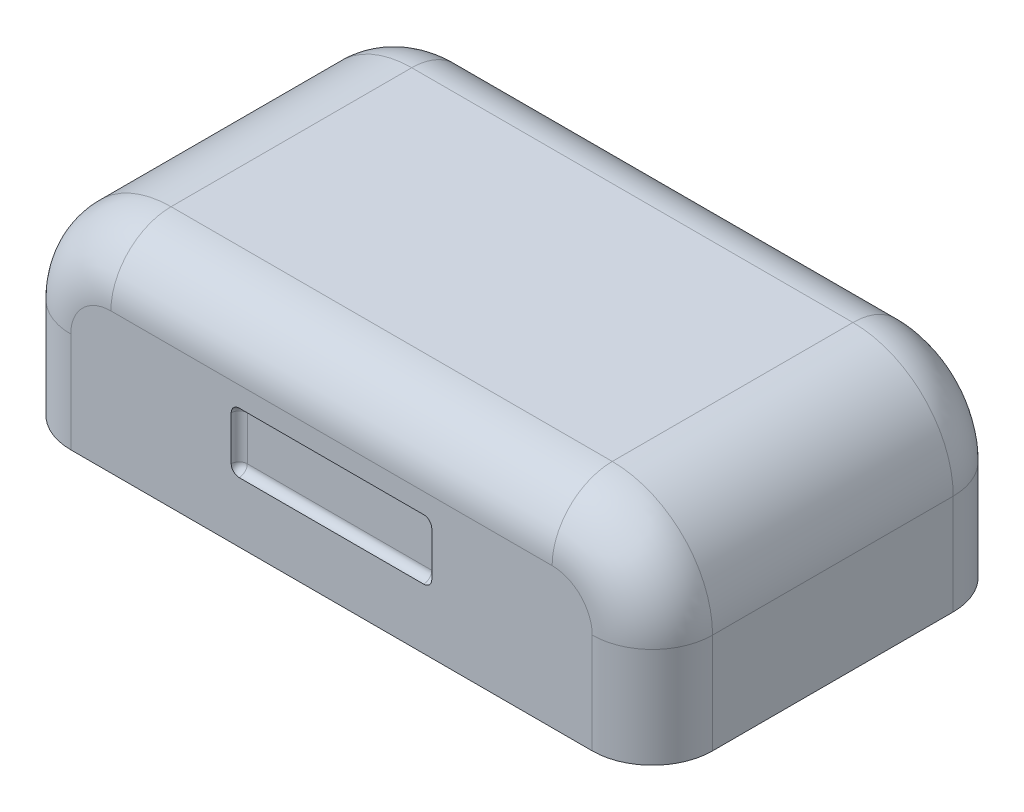
SolidWorks part; units mm, degrees
ref_plane "Plan de face" through (0, 0, 0) normal (0, 0, 1) x (1, 0, 0)
ref_plane "Plan de dessus" through (0, 0, 0) normal (0, 1, 0) x (1, 0, 0)
ref_plane "Plan de droite" through (0, 0, 0) normal (1, 0, 0) x (0, 0, -1)
sketch "Esquisse1" plane through (0, 0, 0) normal (0, 1, 0) x (1, 0, 0)
  line L1 (-44.6588, 68.7058) -> (115.3412, 68.7058)
  line L2 (-44.6588, 68.7058) -> (-44.6588, -21.2942)
  line L3 (-44.6588, -21.2942) -> (115.3412, -21.2942)
  line L4 (115.3412, 68.7058) -> (115.3412, -21.2942)
  dimension "D1" = 90
  dimension "D2" = 160
extrude "Extrusion1" add sketch "Esquisse1" along normal blind 50
fillet "Congé1" radius 25 2 edges at (-44.6588, 50, -23.7058) (115.3412, 50, -23.7058)
fillet "Congé2" radius 15 10 edges at (115.3412, 12.5, 21.2942) (108.0189, 42.6777, 21.2942) (35.3412, 50, 21.2942) (-37.3364, 42.6777, 21.2942) (-44.6588, 12.5, -68.7058) (-37.3364, 42.6777, -68.7058) (35.3412, 50, -68.7058) (108.0189, 42.6777, -68.7058) (-44.6588, 12.5, 21.2942) (115.3412, 12.5, -68.7058)
shell "Coque1" thickness 3 removed face at (35.3412, 0, -23.7058)
sketch "Esquisse2" plane through (0, 0, 21.2942) normal (0, 0, 1) x (1, 0, 0)
  line L0 (-29.6588, 0) -> (100.3412, 0) construction
  line L1 (10.3412, 30) -> (60.3412, 30)
  line L2 (10.3412, 30) -> (10.3412, 15)
  line L3 (10.3412, 15) -> (60.3412, 15)
  line L4 (60.3412, 30) -> (60.3412, 15)
  line L6 (35.3412, 0) -> (35.3412, 35) construction
  line L7 (90.3412, 35) -> (-19.6588, 35) construction
  dimension "D1" = 50
  dimension "D2" = 15
  dimension "D3" = 15
  dimension "D4" = 25
extrude "Enlèv. mat.-Extru.1" cut sketch "Esquisse2" against normal blind 2
fillet "Congé4" radius 2 1 edges at (35.3412, 15, 19.2942) type face fillet first side face at (35.3412, 15, 20.2942) second side face at (35.3412, 22.5, 19.2942)
fillet "Congé5" radius 2 1 edges at (35.3412, 30, 19.2942) type face fillet first side face at (35.3412, 30, 20.2942) second side face at (35.3412, 23.5, 19.2942)
fillet "Congé6" radius 2 1 edges at (10.3412, 22.5, 19.2942) type face fillet first side face at (10.3412, 22.5, 20.0871) second side face at (35.3412, 22.5, 19.2942)
fillet "Congé7" radius 2 1 edges at (60.3412, 22.5, 19.2942) type face fillet first side face at (60.3412, 22.5, 20.0871) second side face at (36.3412, 22.5, 19.2942)
ref_plane "Plan1" through (0, 0, -23.7058) normal (0, 0, 1) x (1, 0, 0)
mirror "Symétrie1" about plane through (0, 0, -23.7058) normal (0, 0, 1) of "Congé7", "Congé6", "Congé5", "Congé4", "Enlèv. mat.-Extru.1"
scale "Echelle1" [suppressed]
